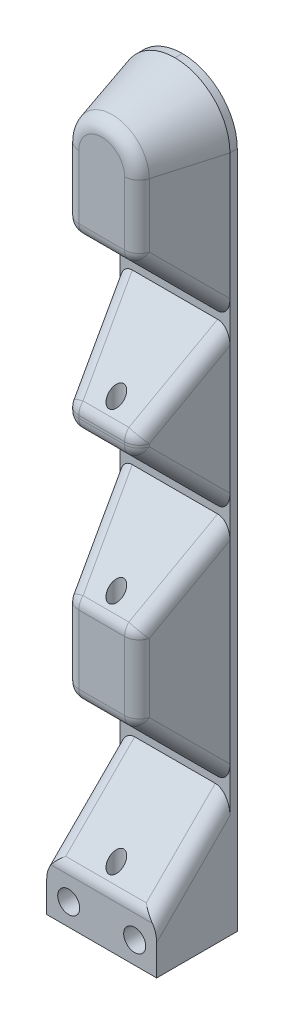
SolidWorks part; units mm, degrees
ref_plane "Plano frontal" through (0, 0, 0) normal (0, 0, 1) x (1, 0, 0)
ref_plane "Plano superior" through (0, 0, 0) normal (0, 1, 0) x (1, 0, 0)
ref_plane "Plano direito" through (0, 0, 0) normal (1, 0, 0) x (0, 0, -1)
sketch "Sketch1" plane through (0, 0, 0) normal (0, 0, 1) x (1, 0, 0)
  line L1 (-15, 100) -> (0, 100)
  line L2 (-15, 100) -> (-15, 0)
  line L3 (-15, 0) -> (0, 0)
  line L4 (0, 100) -> (0, 0)
  dimension "D1" = 15
  dimension "D2" = 100
extrude "Boss-Extrude1" add sketch "Sketch1" along normal blind 1
fillet "Fillet1" radius 7.5 2 edges at (0, 100, 0.5) (-15, 100, 0.5)
sketch "Sketch3" plane through (0, 0, 1) normal (0, 0, 1) x (1, 0, 0)
  line L0 (0, 0) -> (0, 92.5) construction
  line L2 (-15, 92.5) -> (-15, 73)
  line L3 (-15, 73) -> (0, 73)
  line L4 (0, 92.5) -> (0, 73)
  line L5 (-15, 92.5) -> (-15, 0) construction
  line L6 (-15, 72) -> (0, 72)
  line L7 (-15, 72) -> (-15, 50)
  line L8 (-15, 50) -> (0, 50)
  line L9 (0, 72) -> (0, 50)
  line L11 (-15, 49) -> (0, 49)
  line L12 (-15, 49) -> (-15, 17)
  line L13 (-15, 17) -> (0, 17)
  line L14 (0, 49) -> (0, 17)
  line L15 (-15, 0) -> (0, 0)
  line L16 (-15, 0) -> (-15, 18)
  line L17 (-15, 18) -> (0, 18)
  line L18 (0, 0) -> (0, 18)
  arc A0 (0, 92.5) -> (-15, 92.5) centre (-7.5, 92.5) ccw
  line M9 (0, 0) -> (0, 92.5)
  arc M10 (0, 92.5) -> (-7.5, 100) centre (-7.5, 92.5) ccw
  arc M11 (-7.5, 100) -> (-15, 92.5) centre (-7.5, 92.5) ccw
  line M12 (-15, 92.5) -> (-15, 0)
  line M13 (-15, 0) -> (0, 0)
  dimension "D1" = 27
  dimension "D2" = 1
  dimension "D3" = 22
  dimension "D4" = 1
  dimension "D5" = 32
  dimension "D6" = 1
extrude "Boss-Extrude2" add sketch "Sketch3" along normal blind 10 draft 16 contours L3 M12 M9 M10 M11 | L8 L6 M12 M9 | L17 L14 L11 M12 region at (-7.5, 85.7504, 1) region at (-7.5, 61, 1) region at (-7.5, 33.5, 1)
extrude "Boss-Extrude3" add sketch "Sketch3<3>" along normal blind 10 contours L13 M12 M13 M9 region at (-7.5, 8.5, 1)
sketch "Sketch3<3>" plane through (0, 0, 1) normal (0, 0, 1) x (1, 0, 0) same geometry as "Sketch3"
sketch "Sketch4" plane through (0, 0, 0) normal (1, 0, 0) x (0, 0, -1)
  line L0 (-14.6182, 86.6182) -> (-1, 73)
  line L1 (-1, 73) -> (-1, 72)
  line L2 (-1, 72) -> (-12, 61)
  line L4 (-12, 61) -> (-1, 50)
  line L5 (-1, 50) -> (-1, 49)
  line L6 (-1, 49) -> (-14.7138, 35.2862)
  line L7 (-14.7138, 35.2862) -> (-14.7138, 31.7138)
  line L8 (-14.7138, 31.7138) -> (-1, 18)
  line L9 (-1, 18) -> (-1, 17)
  line L10 (-1, 17) -> (-14.3119, 3.6881)
  line L11 (-14.3119, 3.6881) -> (-29.3854, 3.6881)
  line L12 (-29.3854, 3.6881) -> (-29.3854, 86.6182)
  line L13 (-29.3854, 86.6182) -> (-14.6182, 86.6182)
  dimension "D1" = 135
  dimension "D2" = 135
  dimension "D3" = 135
  dimension "D4" = 135
  dimension "D5" = 135
  dimension "D6" = 135
extrude "Cut-Extrude1" cut sketch "Sketch4" against normal through all
sketch "Sketch5" plane through (0, 0, 0) normal (0, -1, 0) x (1, 0, 0)
  line L0 (-15, 11) -> (0, 11) construction
  circle A0 centre (-7.5, 9) radius 1
  dimension "D1" = 2
  dimension "D2" = 2
extrude "Cut-Extrude2" cut sketch "Sketch5" against normal blind 95
fillet "Fillet2" radius 2 25 edges at (-2.8675, 33.5, 11) (-7.5, 28, 11) (-12.1325, 33.5, 11) (-7.5, 39, 11) (-2.8675, 61, 11) (-7.5, 60, 11) (-12.1325, 61, 11) (-7.5, 62, 11) (-12.1325, 87.75, 11) (-7.5, 97.1325, 11) (-2.8675, 87.75, 11) (-7.5, 83, 11) (-7.5, 7, 11) (0, 12, 6) (-15, 12, 6) (-13.5663, 23, 6) (-1.4337, 23, 6) (-1.4337, 44, 6) (-13.5663, 44, 6) (-13.5663, 78, 6) (-1.4337, 78, 6) (-1.4337, 67, 6) (-1.4337, 55, 6) (-13.5663, 55, 6) (-13.5663, 67, 6)
sketch "Sketch6" plane through (0, 0, 11) normal (0, 0, 1) x (1, 0, 0)
  line L0 (-15, 0) -> (0, 0) construction
  line L1 (0, 0) -> (0, 4.1716) construction
  line L2 (-15, 4.1716) -> (-15, 0) construction
  circle A0 centre (-12, 3) radius 1.5
  circle A1 centre (-3, 3) radius 1.5
  point P10 (-15, 2.0858)
  dimension "D1" = 3
  dimension "D2" = 3
  dimension "D3" = 3
  dimension "D4" = 3
  dimension "D5" = 3
  dimension "D6" = 3
extrude "Cut-Extrude3" cut sketch "Sketch6" against normal through all
